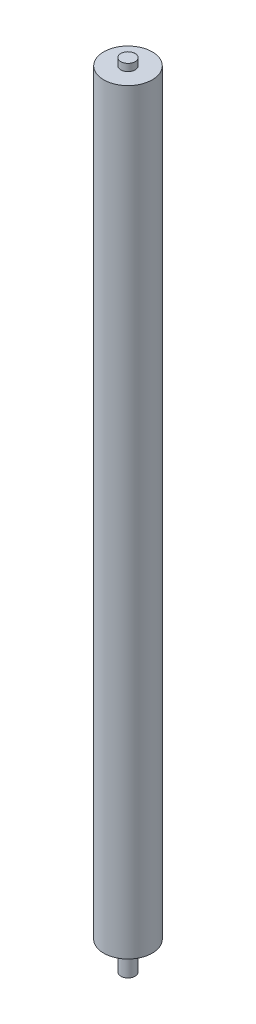
SolidWorks part; units mm, degrees
ref_plane "Front Plane" through (0, 0, 0) normal (0, 0, 1) x (1, 0, 0)
ref_plane "Top Plane" through (0, 0, 0) normal (0, 1, 0) x (1, 0, 0)
ref_plane "Right Plane" through (0, 0, 0) normal (1, 0, 0) x (0, 0, -1)
sketch "Sketch1" plane through (0, 0, 0) normal (0, 1, 0) x (1, 0, 0)
  circle A0 centre (0, 0) radius 10
extrude "Boss-Extrude1" add sketch "Sketch1" along normal blind 40
sketch "Sketch2" plane through (0, 40, 0) normal (0, 1, 0) x (1, 0, 0)
  circle A0 centre (0, 0) radius 34
extrude "Boss-Extrude2" add sketch "Sketch2" along normal blind 1060
sketch "Sketch3" plane through (0, 1100, 0) normal (0, 1, 0) x (1, 0, 0)
  circle A0 centre (0, 0) radius 10
extrude "Boss-Extrude3" add sketch "Sketch3" along normal blind 10
